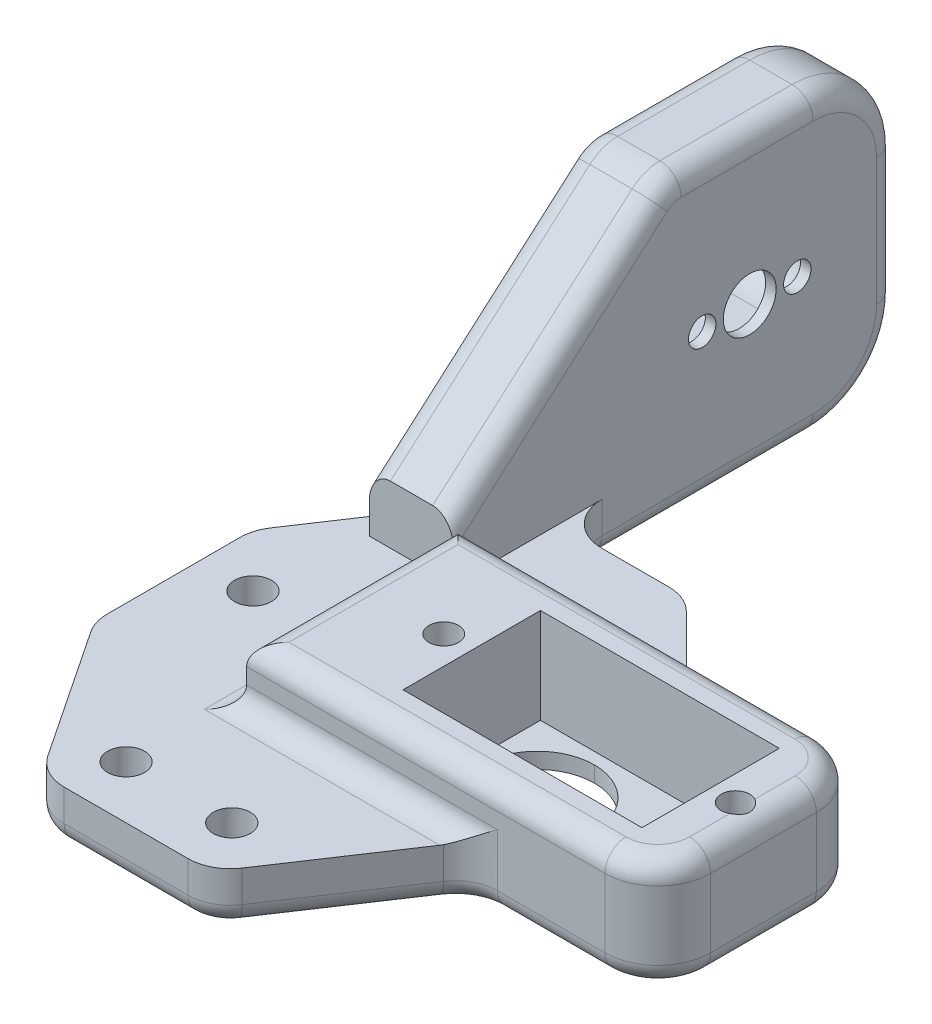
SolidWorks part; units mm, degrees
ref_plane "Front Plane" through (0, 0, 0) normal (0, 0, 1) x (1, 0, 0)
ref_plane "Top Plane" through (0, 0, 0) normal (0, 1, 0) x (1, 0, 0)
ref_plane "Right Plane" through (0, 0, 0) normal (1, 0, 0) x (0, 0, -1)
sketch "Sketch1" plane through (0, 0, 0) normal (0, 1, 0) x (1, 0, 0)
  line L0 (0, 0) -> (45, 0) construction
  line L1 (45, -10) -> (45, 10)
  line L2 (45, 10) -> (21, 10)
  line L3 (21, 10) -> (11.0015, 19.9985)
  line L4 (11.0015, 19.9985) -> (-4.9985, 19.9985)
  line L5 (-4.9985, 19.9985) -> (-14.9997, 4.9966)
  line L6 (-14.9997, 4.9966) -> (-14.9997, -10.0034)
  line L7 (-14.9997, -10.0034) -> (-4.9985, -25.0053)
  line L8 (-4.9985, -25.0053) -> (11.0015, -25.0053)
  line L10 (45, -10) -> (21.005, -10)
  line L11 (21.005, -10) -> (11.0015, -25.0053)
  point P6 (45, 0)
  dimension "D1" = 20
  dimension "D2" = 24
  dimension "D3" = 14.14
  dimension "D4" = 16
  dimension "D5" = 18.03
  dimension "D6" = 15
  dimension "D7" = 146.31
  dimension "D8" = 225
  dimension "D9" = 18.03
  dimension "D10" = 16
  dimension "D11" = 123.69
  dimension "D12" = 123.69
  dimension "D13" = 45
extrude "Boss-Extrude1" add sketch "Sketch1" along normal blind 5
sketch "Sketch2" plane through (0, 5, 0) normal (0, 1, 0) x (1, 0, 0)
  line L0 (45, 0) -> (34.2, 0) construction
  line L1 (45, -10) -> (45, 10) construction
  line L2 (-14.9997, 4.9966) -> (-14.9997, -10.0034) construction
  line L3 (-14.9997, -10.0034) -> (21.005, -10) construction
  line L4 (3.0026, -10.0017) -> (3.0026, -20.0053) construction
  line L5 (-1.9974, -20.0053) -> (8.0026, -20.0053) construction
  line L6 (-4.9985, -25.0053) -> (11.0015, -25.0053) construction
  line L8 (11.5, -5.4) -> (22.3, -5.4)
  line L9 (11.5, -5.4) -> (11.5, 5.4)
  line L10 (11.5, 5.4) -> (22.3, 5.4)
  line L11 (22.3, -5.4) -> (22.3, 5.4)
  line L12 (11.5, -5.4) -> (22.3, 5.4) construction
  line L13 (11.5, 5.4) -> (22.3, -5.4) construction
  circle A0 centre (-9.9997, 0) radius 1.75
  circle A1 centre (-1.9974, -20.0053) radius 1.75
  circle A2 centre (8.0026, -20.0053) radius 1.75
  point P18 (3.0026, -20.0053)
  point P22 (16.9, 0)
  dimension "D2" = 3.5
  dimension "D5" = 3.5
  dimension "D1" = 5
  dimension "D3" = 10
  dimension "D4" = 5
  dimension "D6" = 22.7
  dimension "D7" = 10.8
  dimension "D8" = 10.8
extrude "Cut-Extrude1" cut sketch "Sketch2" against normal through all
fillet "Fillet1" 2 edges at (11.5, 2.5, -5.4) (11.5, 2.5, 5.4) type full round first side face at (16.9, 2.5, -5.4) second side face at (16.9, 2.5, 5.4) middle face at (11.5, 2.5, 0)
fillet "Fillet2" 2 edges at (22.3, 2.5, 5.4) (22.3, 2.5, -5.4) type full round first side face at (19.6, 2.5, 5.4) second side face at (19.6, 2.5, -5.4) middle face at (22.3, 2.5, 0)
fillet "Fillet3" 2 edges at (45, 2.5, 10) (45, 2.5, -10) type full round first side face at (33.0025, 2.5, 10) second side face at (33, 2.5, -10) middle face at (45, 2.5, 0)
sketch "Sketch3" plane through (0, 5, 0) normal (0, 1, 0) x (1, 0, 0)
  line L0 (11.5, 0) -> (22.3, 0) construction
  line L1 (21.005, -10) -> (35, -10) construction
  line L2 (5.4, 6.5) -> (28.4, 6.5)
  line L3 (5.4, 6.5) -> (5.4, -6.5)
  line L4 (5.4, -6.5) -> (28.4, -6.5)
  line L5 (28.4, 6.5) -> (28.4, -6.5)
  line L6 (5.4, 6.5) -> (28.4, -6.5) construction
  line L7 (5.4, -6.5) -> (28.4, 6.5) construction
  line L8 (-0.6, 10) -> (34.4, 10)
  line L9 (-0.6, 10) -> (-0.6, -10)
  line L10 (-0.6, -10) -> (34.4, -10)
  line L11 (34.4, 10) -> (34.4, -10)
  line L12 (-0.6, 10) -> (34.4, -10) construction
  line L13 (-0.6, -10) -> (34.4, 10) construction
  arc A0 (16.9, 5.4) -> (16.9, -5.4) centre (16.9, 0) ccw construction
  arc A1 (16.9, -5.4) -> (16.9, 5.4) centre (16.9, 0) ccw construction
  point P8 (16.9, 0)
  point P13 (16.9, 0)
  dimension "D1" = 6
  dimension "D2" = 13
  dimension "D3" = 23
extrude "Boss-Extrude2" add sketch "Sketch3" along normal blind 5.5
sketch "Sketch4" plane through (0, 5, 0) normal (0, 1, 0) x (1, 0, 0)
  line L4 (5.4, -6.5) -> (28.4, -6.5)
  line L5 (28.4, -6.5) -> (28.4, 6.5)
  line L6 (28.4, 6.5) -> (5.4, 6.5)
  line L7 (5.4, 6.5) -> (5.4, -6.5)
  line L8 (5.4, -6.5) -> (28.4, -6.5)
  line L9 (28.4, -6.5) -> (28.4, 6.5)
  line L10 (28.4, 6.5) -> (5.4, 6.5)
  line L11 (5.4, 6.5) -> (5.4, -6.5)
  dimension "D1" = 0
extrude "Cut-Extrude2" cut sketch "Sketch4" against normal blind 3.5
sketch "Sketch5" plane through (0, 5, 0) normal (0, 1, 0) x (1, 0, 0)
  line L3 (34.4, 10) -> (34.4, -10)
  line L4 (34.4, -10) -> (35, -10)
  line L5 (35, 10) -> (34.4, 10)
  line L6 (34.4, 10) -> (34.4, -10)
  line L7 (34.4, -10) -> (35, -10)
  line L8 (35, 10) -> (34.4, 10)
  arc A1 (35, -10) -> (35, 10) centre (35, 0) ccw
  arc A2 (35, -10) -> (35, 10) centre (35, 0) ccw
  dimension "D1" = 0
extrude "Cut-Extrude3" cut sketch "Sketch5" against normal through all body kept at (21.005, 0, 10)
fillet "Fillet4" radius 4 2 edges at (34.4, 5.25, -10) (34.4, 5.25, 10)
sketch "Sketch6" plane through (0, 0, -19.9985) normal (0, 0, -1) x (-1, 0, 0)
  line L0 (-11.0015, 0) -> (4.9985, 0) construction
  line L1 (0.9985, 0) -> (8.9985, 0)
  line L2 (0.9985, 0) -> (0.9985, 28)
  line L3 (0.9985, 28) -> (8.9985, 28)
  line L4 (8.9985, 0) -> (8.9985, 28)
  line L5 (4.9985, 5) -> (4.9985, 0) construction
  dimension "D1" = 4
  dimension "D2" = 4
  dimension "D3" = 28
extrude "Boss-Extrude3" add sketch "Sketch6" along normal blind 32
sketch "Sketch7" plane through (-0.9985, 0, 0) normal (1, 0, 0) x (0, 0, -1)
  line L0 (51.9985, 0) -> (19.9985, 0) construction
  line L1 (51.9985, 28) -> (51.9985, 0) construction
  line L2 (42.4985, 14) -> (33.4985, 14) construction
  circle A0 centre (37.9985, 14) radius 2.5
  circle A1 centre (33.4985, 14) radius 1.3
  circle A2 centre (42.4985, 14) radius 1.3
  point P9 (37.9985, 14)
  dimension "D1" = 5
  dimension "D5" = 2.6
  dimension "D2" = 14
  dimension "D3" = 14
  dimension "D4" = 9
extrude "Cut-Extrude4" cut sketch "Sketch7" against normal through all
fillet "Fillet5" radius 8 2 edges at (-4.9985, 0, -51.9985) (-4.9985, 28, -51.9985)
sketch "Sketch8" plane through (-8.9985, 0, 0) normal (-1, 0, 0) x (0, 0, 1)
  line L0 (-10, 10.5) -> (-19.9985, 28)
  line L1 (-19.9985, 28) -> (-19.9985, 0)
  line L2 (-19.9985, 0) -> (-10, 0)
  line L3 (-10, 0) -> (-10, 10.5)
extrude "Boss-Extrude6" add sketch "Sketch8" against normal up to surface (8 mm away) up to face at (-0.9985, 14, -43.7985)
sketch "Sketch10" plane through (-8.9985, 0, 0) normal (-1, 0, 0) x (0, 0, 1)
  line L0 (-35.4985, 14) -> (-40.4985, 14) construction
  line L2 (-44.9985, 10.5) -> (-30.9985, 10.5)
  line L3 (-44.9985, 10.5) -> (-44.9985, 17.5)
  line L4 (-44.9985, 17.5) -> (-30.9985, 17.5)
  line L5 (-30.9985, 10.5) -> (-30.9985, 17.5)
  line L6 (-44.9985, 10.5) -> (-30.9985, 17.5) construction
  line L7 (-44.9985, 17.5) -> (-30.9985, 10.5) construction
  circle A0 centre (-37.9985, 14) radius 2.5 construction
  point P5 (-37.9985, 14)
  dimension "D1" = 7
  dimension "D2" = 14
extrude "Cut-Extrude5" cut sketch "Sketch10" against normal blind 7
fillet "Fillet6" 2 edges at (-5.4985, 17.5, -30.9985) (-5.4985, 10.5, -30.9985) type full round first side face at (-5.4985, 17.5, -37.9985) second side face at (-5.4985, 10.5, -37.9985) middle face at (-5.4985, 14, -30.9985)
fillet "Fillet7" 2 edges at (-5.4985, 10.5, -44.9985) (-5.4985, 17.5, -44.9985) type full round first side face at (-5.4985, 10.5, -39.7485) second side face at (-5.4985, 17.5, -39.7485) middle face at (-5.4985, 14, -44.9985)
sketch "Sketch11" plane through (-8.9985, 0, 0) normal (-1, 0, 0) x (0, 0, 1)
  line L0 (-10, 10.5) -> (-29.9985, 28)
  line L1 (-43.9985, 28) -> (-19.9985, 28) construction
  line L2 (-29.9985, 28) -> (-19.9985, 28)
  line L3 (-19.9985, 28) -> (-10, 10.5)
  dimension "D1" = 10
extrude "Cut-Extrude6" cut sketch "Sketch11" against normal through all
fillet "Fillet8" radius 4 10 edges at (-0.9985, 2.5, -19.9985) (11.0015, 2.5, -19.9985) (21, 2.5, -10) (21.005, 2.5, 10) (11.0015, 2.5, 25.0053) (-4.9985, 2.5, 25.0053) (-14.9997, 2.5, 10.0034) (-14.9997, 2.5, -4.9966) (-8.9985, 2.5, -13.9985) (-4.9985, 28, -29.9985)
sketch "Sketch12" plane through (0, 1.5, 0) normal (0, 1, 0) x (1, 0, 0)
  line L0 (5.4, -6.5) -> (28.4, -6.5) construction
  line L1 (5.4, 6.5) -> (10.7, 6.5)
  line L2 (5.4, 6.5) -> (5.4, -6.5)
  line L3 (5.4, -6.5) -> (10.7, -6.5)
  line L4 (10.7, 6.5) -> (10.7, -6.5)
  line L5 (5.4, 0) -> (10.7, 0) construction
  circle A0 centre (8.05, 0) radius 1.4
  dimension "D2" = 2.8
  dimension "D1" = 5.3
extrude "Boss-Extrude7" add sketch "Sketch12" along normal up to surface (9 mm away) up to face at (21.6761, 10.5, 0)
sketch "Sketch13" plane through (0, 10.5, 0) normal (0, 1, 0) x (1, 0, 0)
  line L0 (30.4, 10) -> (38.3, 10)
  line L1 (30.4, -10) -> (38.3, -10)
  line L2 (38.3, -10) -> (38.3, 10)
  line L3 (34.4, -6) -> (34.4, 6) construction
  line L4 (34.4, -6) -> (34.4, 6)
  arc A0 (30.4, -10) -> (34.4, -6) centre (30.4, -6) ccw construction
  arc A1 (34.4, 6) -> (30.4, 10) centre (30.4, 6) ccw construction
  arc A2 (30.4, -10) -> (34.4, -6) centre (30.4, -6) ccw
  arc A3 (34.4, 6) -> (30.4, 10) centre (30.4, 6) ccw
  dimension "D1" = 7.9
extrude "Boss-Extrude8" add sketch "Sketch13" against normal up to surface (10.5 mm away) up to face at (6.8206, 0, -3.7768)
sketch "Sketch14" plane through (0, 10.5, 0) normal (0, 1, 0) x (1, 0, 0)
  line L0 (8.05, 0) -> (35.65, 0) construction
  circle A0 centre (35.65, 0) radius 1.35
  dimension "D2" = 2.7
  dimension "D1" = 27.6
extrude "Cut-Extrude7" cut sketch "Sketch14" against normal up to surface (9 mm away) up to face at (8.05, 1.5, 1.4)
fillet "Fillet9" radius 5 2 edges at (38.3, 5.25, 10) (38.3, 5.25, -10)
sketch "Sketch15" plane through (0, 10.5, 0) normal (0, 1, 0) x (1, 0, 0)
  line L0 (10.7, -6.5) -> (28.4, -6.5) construction
  line L1 (28.4, 6.5) -> (33.3, 6.5)
  line L2 (28.4, 6.5) -> (28.4, -6.5)
  line L3 (28.4, -6.5) -> (33.3, -6.5)
  line L4 (33.3, 6.5) -> (33.3, -6.5)
  dimension "D1" = 4.9
extrude "Cut-Extrude8" cut sketch "Sketch15" against normal up to surface (9 mm away) up to face at (19.55, 1.5, 0)
fillet "Fillet10" radius 2 44 edges at (16.35, 10.5, 10) (36.8355, 10.5, 8.5355) (38.3, 10.5, 0) (36.8355, 10.5, -8.5355) (-0.9985, 18.7551, -19.4337) (-0.9985, 27.7444, -30.0945) (-0.9985, 28, -37.75) (-0.9985, 25.6569, -49.6553) (-0.9985, 14, -51.9985) (-0.9985, 2.3431, -49.6553) (-0.9985, 0, -33.9985) (0.1731, 0, -21.1701) (6.1731, 0, -19.9985) (10.8754, 0, -19.694) (16.0008, 0, -14.9992) (21.1261, 0, -10.3045) (27.9784, 0, -10) (-8.9985, 18.7551, -19.4337) (-8.9985, 27.7444, -30.0945) (-8.9985, 28, -37.75) (-8.9985, 25.6569, -49.6553) (-8.9985, 14, -51.9985) (-8.9985, 2.3431, -49.6553) (-8.9985, 0, -29.604) (-9.1701, 0, -14.0504) (-11.9991, 0, -9.4975) (-14.8281, 0, -4.9446) (-14.9997, 0, 2.5034) (-14.8281, 0, 9.9514) (-10.2569, 0, 17.1176) (-4.7452, 0, 24.532) (3.0015, 0, 25.0053) (10.7482, 0, 24.532) (16.0033, 0, 17.5026) (21.2583, 0, 10.4733) (28.2229, 0, 10) (36.8355, 0, 8.5355) (38.3, 0, 0) (11.2729, 5, 10) (-0.6, 5, 0) (-0.6, 10.5, 0) (16.35, 10.5, -10) (11.0284, 5, -10) (36.8355, 0, -8.5355)
